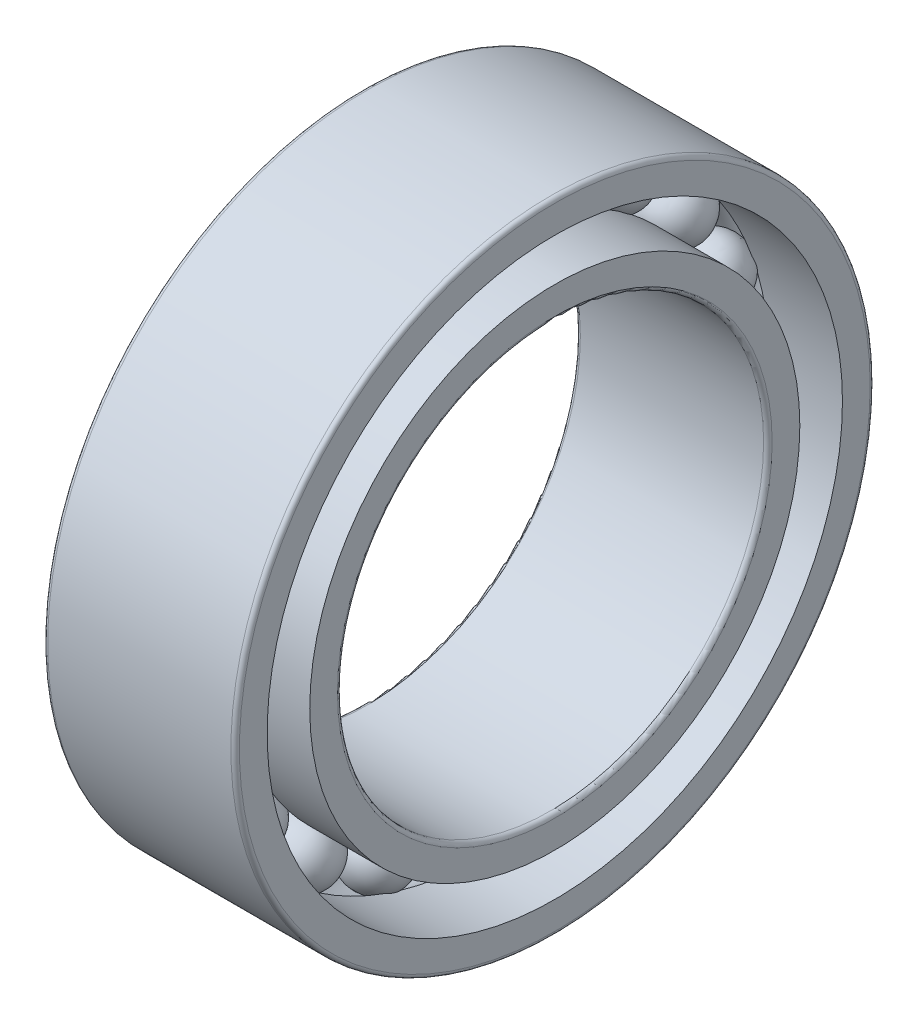
SolidWorks part; units mm, degrees
ref_plane "Plane1" through (0, 0, 0) normal (0, 0, 1) x (1, 0, 0)
ref_plane "Plane2" through (0, 0, 0) normal (0, 1, 0) x (1, 0, 0)
ref_plane "Plane3" through (0, 0, 0) normal (1, 0, 0) x (0, 0, -1)
sketch "Clipboard" plane through (0, 0, 0) normal (0, 0, 1) x (1, 0, 0)
  line L0 (-10, 0) -> (10, 0) construction
  line L1 (0, 0) -> (21.0122, -7.6478)
  line L2 (0, 0) -> (5.8731, 2.1376)
  line L3 (0, 0) -> (21.0122, -7.6478)
  line L4 (0, 0) -> (-22.3573, -0.3902)
  dimension "BallCLRad" = 6.25
sketch "CagSpiSke" plane through (0, 0, 0) normal (0, 0, 1) x (1, 0, 0)
  line L0 (0.075, 6.125) -> (0.075, 6.375)
  line L1 (0.075, 6.375) -> (-0.075, 6.375)
  line L2 (-0.075, 6.375) -> (-0.075, 6.125)
  line L3 (-0.075, 6.125) -> (0.075, 6.125)
  line L4 (-20.6375, 0) -> (20.6375, 0) construction
  line L5 (0, 0) -> (0, 23.7692) construction
  dimension "OD" = 12.75
  dimension "ID" = 12.25
revolve "CageSpine" add sketch "CagSpiSke" angle 0.001 about L4 reverse direction yes
ref_axis "Axis1" through (-50, 0, 0) along (1, 0, 0)
sketch "CagBalSke" plane through (0, 0, 0) normal (0, 0, 1) x (1, 0, 0)
  line L0 (-0.825, 6.25) -> (0.825, 6.25)
  line L1 (-1.905, 6.25) -> (1.905, 6.25) construction
  line L2 (-10, 0) -> (10, 0) construction
  line L3 (0, 0) -> (0, 24) construction
  arc A0 (0.825, 6.25) -> (-0.825, 6.25) centre (0, 6.25) cw
  dimension "BallCLRad" = 6.25
revolve "CageBall" [suppressed] add sketch "CagBalSke" angle 360 about L1 reverse direction yes
pattern_circular "CageBalls" [suppressed] count 20 every 18 about axis through (-50, 0, 0) along (1, 0, 0)
sketch "CagTrmODSke" plane through (0, 0, 0) normal (0, 0, 1) x (1, 0, 0)
  line L0 (0.826, 6.375) -> (0.826, 7.076)
  line L1 (0.826, 7.076) -> (-0.826, 7.076)
  line L2 (-0.826, 7.076) -> (-0.826, 6.375)
  line L3 (-0.826, 6.375) -> (0.826, 6.375)
  line L4 (-20.6375, 0) -> (20.6375, 0) construction
  line L5 (0, 0) -> (0, 25) construction
  dimension "Width" = 1.652
  dimension "ID" = 12.75
  dimension "OD" = 14.152
revolve "CageTrimOD" [suppressed] cut sketch "CagTrmODSke" angle 360 about L4 reverse direction yes
sketch "CagTrmIDSke" plane through (0, 0, 0) normal (0, 0, 1) x (1, 0, 0)
  line L0 (0.826, 5.426) -> (0.826, 6.125)
  line L1 (0.826, 6.125) -> (-0.826, 6.125)
  line L2 (-0.826, 6.125) -> (-0.826, 5.426)
  line L3 (-0.826, 5.426) -> (0.826, 5.426)
  line L4 (-20.6375, 0) -> (20.6375, 0) construction
  line L5 (0, 0) -> (0, 25) construction
  dimension "Width" = 1.652
  dimension "ID" = 10.852
  dimension "OD" = 12.25
revolve "CageTrimID" [suppressed] cut sketch "CagTrmIDSke" angle 360 about L4 reverse direction yes
sketch "BalSimSke" plane through (0, 0, 0) normal (0, 0, 1) x (1, 0, 0)
  line L0 (-10, 0) -> (10, 0) construction
  line L1 (-10, 6.25) -> (10, 6.25) construction
  line L2 (0, 0) -> (0, 23) construction
  circle A0 centre (0, 6.25) radius 0.75
  dimension "BallCLRad" = 6.25
  dimension "Ball_diameter" = 1.5
revolve "BallsSimplified" [suppressed] add sketch "BalSimSke" angle 360 about L0
sketch "BalDetSke" plane through (0, 0, 0) normal (0, 0, 1) x (1, 0, 0)
  line L0 (-0.75, 6.25) -> (0.75, 6.25)
  line L1 (-1.905, 6.25) -> (1.905, 6.25) construction
  line L2 (0, 0) -> (0, 25) construction
  arc A0 (0.75, 6.25) -> (-0.75, 6.25) centre (0, 6.25) cw
  dimension "BallCLRad" = 6.25
  dimension "Ball_diameter" = 1.5
revolve "BallDetailed" add sketch "BalDetSke" angle 360 about L1 reverse direction yes
sketch "InnRacSke" plane through (0, 0, 0) normal (0, 0, 1) x (1, 0, 0)
  line L0 (-0.525, 5.75) -> (-2.25, 5.75)
  line L1 (-2.25, 5.75) -> (-2.25, 5.1)
  line L2 (-2.15, 5) -> (2.15, 5)
  line L3 (2.25, 5.1) -> (2.25, 5.75)
  line L4 (2.25, 5.75) -> (0.525, 5.75)
  line L5 (-20.6375, 0) -> (20.6375, 0) construction
  line L6 (0, 0) -> (0, 30) construction
  arc A0 (-2.25, 5.1) -> (-2.15, 5) centre (-2.15, 5.1) ccw
  arc A1 (2.15, 5) -> (2.25, 5.1) centre (2.15, 5.1) ccw
  arc A2 (0.525, 5.75) -> (-0.525, 5.75) centre (0, 6.25) cw
  dimension "BallCLRad" = 6.25
  dimension "Fillet_radius" = 0.1
  dimension "Ball_diameter" = 1.45
  dimension "ID" = 10
  dimension "OD" = 11.5
  dimension "Width" = 4.5
revolve "InnerRace" add sketch "InnRacSke" angle 360 about L5 reverse direction yes
sketch "OutRacSke" plane through (0, 0, 0) normal (0, 0, 1) x (1, 0, 0)
  line L0 (-0.525, 6.75) -> (-2.25, 6.75)
  line L1 (-2.25, 6.75) -> (-2.25, 7.4)
  line L2 (-2.15, 7.5) -> (2.15, 7.5)
  line L3 (2.25, 7.4) -> (2.25, 6.75)
  line L4 (2.25, 6.75) -> (0.525, 6.75)
  line L5 (-20.6375, 0) -> (20.6375, 0) construction
  line L6 (0, 0) -> (0, 30) construction
  arc A0 (-2.25, 7.4) -> (-2.15, 7.5) centre (-2.15, 7.4) cw
  arc A1 (2.15, 7.5) -> (2.25, 7.4) centre (2.15, 7.4) cw
  arc A2 (0.525, 6.75) -> (-0.525, 6.75) centre (0, 6.25) ccw
  dimension "BallCLRad" = 6.25
  dimension "Fillet_radius" = 0.1
  dimension "Ball_diameter" = 1.45
  dimension "Width" = 4.5
revolve "OuterRace" add sketch "OutRacSke" angle 360 about L5 reverse direction yes
pattern_circular "BallsDetailed" count 20 every 18 about axis through (-50, 0, 0) along (1, 0, 0) of "BallDetailed"
equation "\"BallCLRad@Clipboard\" = ( \"OD@OutRacSke\" + \"ID@InnRacSke\" ) / 4"
equation "\"BallCLRad@BalSimSke\" = \"BallCLRad@Clipboard\""
equation "\"BallCLRad@BalDetSke\" = \"BallCLRad@Clipboard\""
equation "\"BallCLRad@InnRacSke\" = \"BallCLRad@Clipboard\""
equation "\"BallCLRad@OutRacSke\" = \"BallCLRad@Clipboard\""
equation "\"Ball_diameter@InnRacSke\" = \"Ball_diameter@BalDetSke\" - 0.05"
equation "\"Ball_diameter@OutRacSke\" = \"Ball_diameter@BalDetSke\" - 0.05"
equation "\"Ball_diameter@BalSimSke\" = \"Ball_diameter@BalDetSke\""
equation "\"Width@OutRacSke\" = \"Width@InnRacSke\""
equation "\"Fillet_radius@OutRacSke\" = \"Fillet_radius@InnRacSke\""
equation "\"Max_count@Clipboard\" = int( 3.14159265 / atn(( \"Ball_diameter@BalDetSke\" / 2) / sqr( \"BallCLRad@Clipboard\"  *  \"BallCLRad@Clipboard\" - ( \"Ball_diameter@BalDetSke\" / 2) *  ( \"Ball_diameter@BalDetSke\" / 2))))"
equation "\"Max_count@Clipboard\" = ((sgn( \"Max_count@Clipboard\" - \"Count@Clipboard\" )-1)*( \"Max_count@Clipboard\" - \"Count@Clipboard\" ))/-2+ \"Count@Clipboard\""
equation "\"Count@BallsDetailed\" = int( \"Show_count@Clipboard\" ) "
equation "\"Count@BallsDetailed\" = ((sgn( \"Count@BallsDetailed\" - \"Max_count@Clipboard\" )-1)*( \"Count@BallsDetailed\" - \"Max_count@Clipboard\" ))/-2+ \"Max_count@Clipboard\""
equation "\"Count@BallsDetailed\" = ((sgn( \"Count@BallsDetailed\" - \"Min_count@Clipboard\" )+1)*( \"Count@BallsDetailed\" - \"Min_count@Clipboard\"))/2 +\"Min_count@Clipboard\""
equation "\"Angle@BallsDetailed\" = 360.0 / \"Max_count@Clipboard\""
equation "\"BallCLRad@CagBalSke\" = \"BallCLRad@Clipboard\""
equation "\"Count@CageBalls\" = \"Count@BallsDetailed\""
equation "\"Angle@CageBalls\" = \"Angle@BallsDetailed\""
equation "\"Angle@CageSpine\" =  \"Angle@CageBalls\" * ( \"Count@CageBalls\" -1 + int( \"Count@CageBalls\" / \"Max_count@Clipboard\" ) )  + 0.001 -  int( \"Count@CageBalls\" / \"Max_count@Clipboard\" ) * 0.001"
equation "\"Angle@CageSpine\" =  \"Angle@CageSpine\" * int( \"Min_count@Clipboard\" / 2) + int(1 / \"Min_count@Clipboard\")  * 0.001"
equation "\"CageWallOD@CagBalSke\" =  \"Ball_diameter@BalDetSke\" * 1.1"
equation "\"Thickness@CagSpiSke\" =  \"Ball_diameter@BalDetSke\" * 0.1"
equation "\"OD@CagTrmODSke\" = \"BallCLRad@Clipboard\" * 2 + \"CageWallOD@CagBalSke\" + 0.002"
equation "\"ID@CagTrmODSke\" = \"BallCLRad@Clipboard\" * 2 + \"Ball_diameter@BalDetSke\" / 6"
equation "\"OD@CagTrmIDSke\" = \"BallCLRad@Clipboard\" * 2 - \"Ball_diameter@BalDetSke\" / 6"
equation "\"ID@CagTrmIDSke\" = \"BallCLRad@Clipboard\" * 2 - \"CageWallOD@CagBalSke\" + 0.002"
equation "\"OD@CagSpiSke\" = \"ID@CagTrmODSke\""
equation "\"ID@CagSpiSke\" = \"OD@CagTrmIDSke\""
equation "\"Width@CagTrmODSke\" = \"CageWallOD@CagBalSke\" + 0.002"
equation "\"Width@CagTrmIDSke\" = \"CageWallOD@CagBalSke\" + 0.002"
